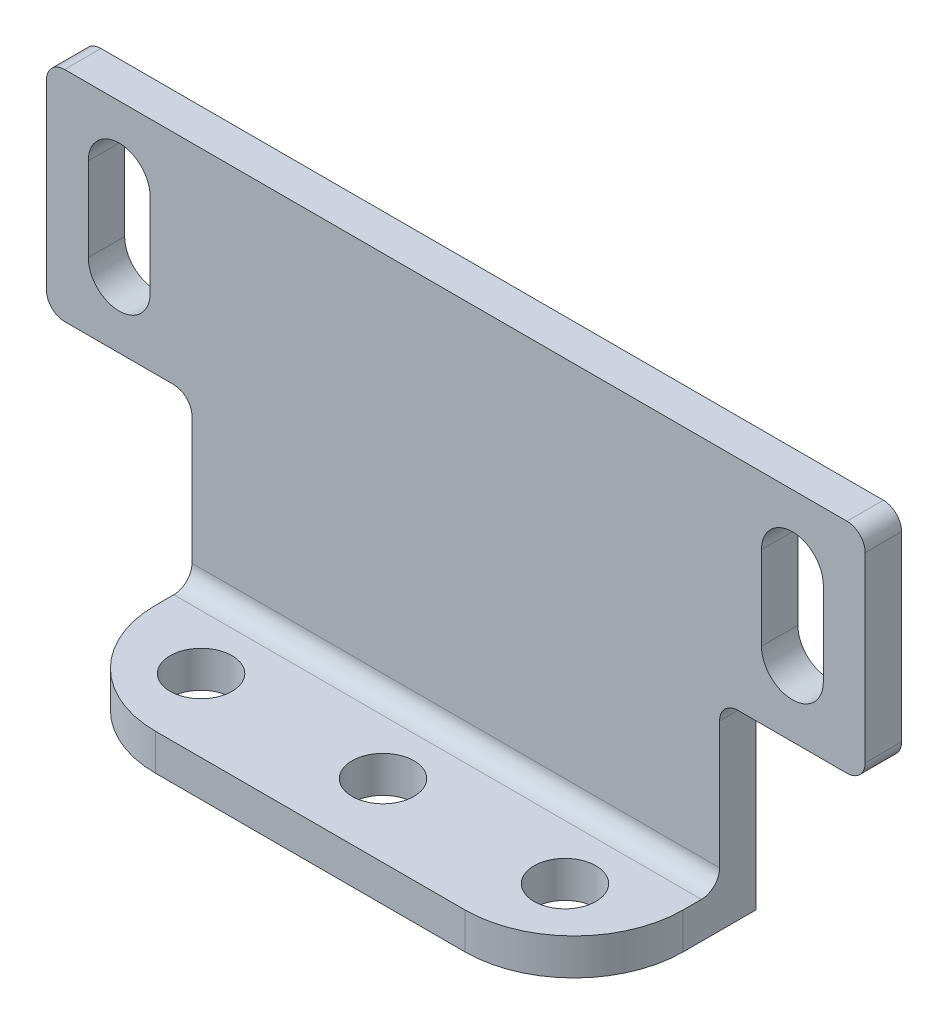
SolidWorks part; units mm, degrees
ref_plane "前视基准面" through (0, 0, 0) normal (0, 0, 1) x (1, 0, 0)
ref_plane "上视基准面" through (0, 0, 0) normal (0, 1, 0) x (1, 0, 0)
ref_plane "右视基准面" through (0, 0, 0) normal (1, 0, 0) x (0, 0, -1)
sketch "草图1" plane through (0, 0, 0) normal (0, 0, 1) x (1, 0, 0)
  line L1 (-22.5, 5) -> (22.5, 5)
  line L2 (-22.5, 5) -> (-22.5, -5)
  line L3 (-22.5, -5) -> (22.5, -5)
  line L4 (22.5, 5) -> (22.5, -5)
  line L5 (-22.5, 5) -> (22.5, -5) construction
  line L6 (-22.5, -5) -> (22.5, 5) construction
  point P0 (0, 0)
  dimension "D1" = 45
  dimension "D2" = 10
extrude "凸台-拉伸1" add sketch "草图1" along normal blind 2
sketch "草图2" plane through (0, 0, 0) normal (0, 0, 1) x (1, 0, 0)
  line L0 (22.5, -5) -> (22.5, 5) construction
  line L1 (-22.5, 5) -> (22.5, 5)
  line L2 (-22.5, 5) -> (-22.5, -18)
  line L3 (-22.5, -18) -> (22.5, -18)
  line L4 (22.5, 5) -> (22.5, -18)
  dimension "D1" = 23
extrude "凸台-拉伸2" add sketch "草图2" along normal blind 2
sketch "草图4" plane through (0, 0, 0) normal (0, 0, 1) x (1, 0, 0)
  line L0 (22.5, -18) -> (22.5, 5) construction
  line L1 (-22.5, -18) -> (22.5, -18)
  line L2 (-22.5, -18) -> (-22.5, -16)
  line L3 (-22.5, -16) -> (22.5, -16)
  line L4 (22.5, -18) -> (22.5, -16)
  dimension "D1" = 2
extrude "凸台-拉伸3" add sketch "草图4" along normal blind 10
hole_wizard "M3 间隙孔1" positions "草图5" profile "草图6" hole size "M3" standard "GB"
sketch "草图5" plane through (0, -16, 0) normal (0, 1, 0) x (1, 0, 0)
  line L0 (0, 0) -> (0, -29.3146) construction
  line L2 (-22.5, -10) -> (-22.5, -2) construction
  line L3 (-22.5, -6) -> (-29.32, -6) construction
  point P0 (-10, -6)
  dimension "D1" = 10
sketch "草图6" plane through (-10, -16, 6) normal (1, 0, 0) x (0, 0, 1)
  line L0 (0, 0) -> (0, 9.5215)
  line L1 (0, 9.5215) -> (1.7, 8.5)
  line L2 (1.7, 8.5) -> (1.7, 0)
  line L5 (1.7, 0) -> (0, 0)
  line L10 (0, 9.5215) -> (-1.7, 8.5) construction
  line L11 (0, -6.35) -> (0, 107.95) construction
  dimension "孔直径" = 3.4
  dimension "孔深度" = 8.5
  dimension "导头角度" = 118
pattern_linear "阵列(线性)1" count 3 spacing 10 along (1, 0, 0) of "M3 间隙孔1"
hole_wizard "M3 间隙槽口2" positions "草图7" profile "草图8" size "M3" standard "GB" slot yes
sketch "草图7" plane through (0, 0, 0) normal (0, 0, -1) x (-1, 0, 0)
  line L0 (18.5, -5) -> (18.5, 3) construction
  line L1 (0, 0) -> (0, -55.6486) construction
  point P0 (18.5, -1)
  point P4 (-18.5, -1)
  dimension "D1" = 8
  dimension "D2" = 37
  dimension "D3" = 3
sketch "草图8" plane through (-18.5, -1, 0) normal (1, 0, 0) x (0, 1, 0)
  line L0 (0, 0) -> (0, 9.5215)
  line L1 (0, 9.5215) -> (1.7, 8.5)
  line L2 (1.7, 8.5) -> (1.7, 0)
  line L5 (1.7, 0) -> (0, 0)
  line L10 (0, 9.5215) -> (-1.7, 8.5) construction
  line L11 (0, -6.35) -> (0, 107.95) construction
  dimension "孔直径" = 3.4
  dimension "孔深度" = 8.5
  dimension "导头角度" = 118
sketch "草图9" plane through (0, 0, 2) normal (0, 0, 1) x (1, 0, 0)
  line L0 (-22.5, -16) -> (22.5, -16) construction
  line L1 (-22.5, -18) -> (-14.5, -18)
  line L2 (-22.5, -18) -> (-22.5, -16)
  line L3 (-22.5, -16) -> (-14.5, -16)
  line L4 (-14.5, -18) -> (-14.5, -16)
  line L5 (22.5, -16) -> (-22.5, -16) construction
  line L6 (22.5, -18) -> (14.5, -18)
  line L7 (22.5, -18) -> (22.5, -16)
  line L8 (22.5, -16) -> (14.5, -16)
  line L9 (14.5, -18) -> (14.5, -16)
  dimension "D1" = 8
  dimension "D2" = 8
extrude "切除-拉伸1" cut sketch "草图9" along normal through all
fillet "圆角1" radius 6 2 edges at (14.5, -17, 10) (-14.5, -17, 10)
fillet "圆角3" radius 1 1 edges at (0, -16, 2)
sketch "草图11" plane through (0, 0, 2) normal (0, 0, 1) x (1, 0, 0)
  line L1 (-22.5, -18) -> (-14.5, -18)
  line L2 (-22.5, -18) -> (-22.5, -7)
  line L3 (-22.5, -7) -> (-14.5, -7)
  line L4 (-14.5, -18) -> (-14.5, -7)
  dimension "D1" = 11
  dimension "D2" = 8
extrude "切除-拉伸2" cut sketch "草图11" against normal up to next
mirror "镜向1" about plane through (0, 0, 0) normal (1, 0, 0) of "切除-拉伸2"
fillet "圆角5" radius 1 6 edges at (22.5, 5, 1) (22.5, -7, 1) (14.5, -7, 1) (-22.5, 5, 1) (-22.5, -7, 1) (-14.5, -7, 1)
